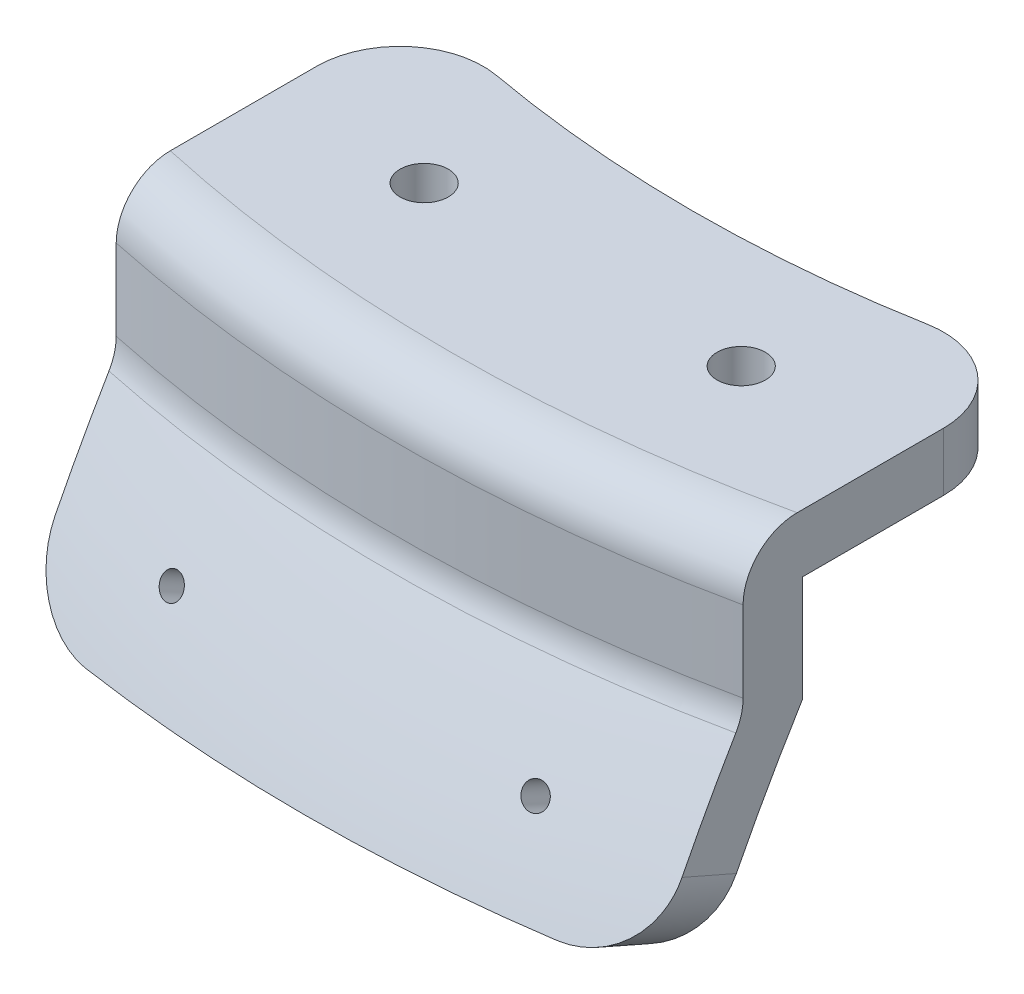
SolidWorks part; units mm, degrees
material "Polyether Polyol"
ref_plane "Front Plane" through (0, 0, 0) normal (0, 0, 1) x (1, 0, 0)
ref_plane "Top Plane" through (0, 0, 0) normal (0, 1, 0) x (1, 0, 0)
ref_plane "Right Plane" through (0, 0, 0) normal (1, 0, 0) x (0, 0, -1)
sketch "Sketch2" plane through (0, 0, 0) normal (1, 0, 0) x (0, 0, -1)
  line L0 (-174.1012, 207.3685) -> (-174.1012, 194.6685) construction
  line L1 (-192.235, 174.9156) -> (-185.8333, 172.084) construction
  line L2 (-181.1012, 214.3685) -> (-181.1012, 196.5948) construction
  line L3 (-181.1012, 214.3685) -> (-145.5262, 214.3685) construction
  line L4 (-145.5262, 214.3685) -> (-145.5262, 207.3685) construction
  line L5 (-145.5262, 207.3685) -> (-174.1012, 207.3685) construction
  line L12 (0, 89.8878) -> (0, 207.3685) construction
  line L13 (-174.1012, 207.3685) -> (-174.1012, 194.6685)
  line L14 (-192.235, 174.9156) -> (-185.8333, 172.084)
  line L15 (-181.1012, 214.3685) -> (-181.1012, 196.5948)
  line L16 (-181.1012, 214.3685) -> (-145.5262, 214.3685)
  line L17 (-145.5262, 214.3685) -> (-145.5262, 207.3685)
  line L18 (-145.5262, 207.3685) -> (-174.1012, 207.3685)
  arc A0 (-174.1012, 194.6685) -> (-185.8333, 172.084) centre (0, 89.8878) ccw construction
  arc A1 (-181.1012, 196.5948) -> (-192.235, 174.9156) centre (0, 89.8878) ccw construction
  arc A4 (-174.1012, 194.6685) -> (-185.8333, 172.084) centre (0, 89.8878) ccw
  arc A5 (-181.1012, 196.5948) -> (-192.235, 174.9156) centre (0, 89.8878) ccw
revolve "Revolve1" add sketch "Sketch2" angle 30 mid plane about L12 other way angle 30
fillet "Fillet1" radius 6.35 2 edges at (0, 196.5948, 181.1012) (0, 214.3685, 181.1012)
sketch "Sketch3" plane through (0, 214.3685, 0) normal (0, -1, 0) x (1, 0, 0)
  circle A2 centre (-19.05, 158.75) radius 3.5719 construction
  circle A3 centre (19.05, 158.75) radius 3.5719 construction
  circle A4 centre (19.05, 158.75) radius 2.9
  circle A5 centre (-19.05, 158.75) radius 2.9
  dimension "D1" = 5.8
extrude "Cut-Extrude1" cut sketch "Sketch3" along normal through all contours A4 | A5 region at (19.05, 214.3685, 158.75) region at (-19.05, 214.3685, 158.75)
sketch "Sketch4" plane through (0, 214.3685, 0) normal (0, 1, 0) x (1, 0, 0)
  line L0 (37.665, -140.5675) -> (45.2289, -168.7967) construction
  line L1 (37.665, -140.5675) -> (-37.665, -140.5675)
  line L2 (37.665, -140.5675) -> (37.665, -192.235)
  line L3 (37.665, -192.235) -> (-37.665, -192.235)
  line L4 (-37.665, -140.5675) -> (-37.665, -192.235)
  line L5 (-37.665, -140.5675) -> (-45.2289, -168.7967) construction
  arc A0 (-37.665, -140.5675) -> (37.665, -140.5675) centre (0, 0) ccw construction
  arc A1 (-49.7541, -185.6848) -> (49.7541, -185.6848) centre (0, 0) ccw construction
  point P5 (37.665, -140.5675)
  point P12 (37.665, -201.1133)
  point P16 (-37.665, -140.5675)
extrude "Cut-Extrude2" cut sketch "Sketch4" against normal through all flip side to cut
fillet "Fillet2" radius 10 4 edges at (-37.665, 210.8685, 140.5675) (37.665, 210.8685, 140.5675)
sketch "Sketch5" plane through (0, 0, 0) normal (-1, 0, 0) x (0, 0, 1)
  line L0 (0, 89.8878) -> (181.0525, 182.1386) construction
  line L2 (0, -200000) -> (0, 218797.9879) construction
  arc A0 (185.8333, 172.084) -> (174.1012, 194.6685) centre (0, 89.8878) ccw construction
  point P3 (169.9388, 179.5463)
  point P4 (0, 89.8878)
  point P5 (179.5114, 185.1028)
  dimension "D1" = 63
ref_plane "Plane1" through (0, 71.3612, -36.3604) normal (0, 0.891, -0.454) x (0, 0.454, 0.891)
sketch "Sketch6" plane through (0, 71.3612, -36.3604) normal (0, 0.891, -0.454) x (0, 0.454, 0.891)
  line L0 (216.935, 18.9794) -> (275.7942, 24.1289) construction
  line L2 (216.935, 18.9794) -> (275.7942, 24.1289)
  line L3 (216.935, 18.9794) -> (216.8043, 20.4736)
  line L4 (275.7942, 24.1289) -> (275.6635, 25.6232)
  line L5 (216.8043, 20.4736) -> (275.6635, 25.6232)
  line L6 (40.8082, 0) -> (244.0082, 0) construction
  ellipse E0 centre (88.3777, 0) end of major axis (88.3777, 145.5262) minor radius 129.6648 construction
  point P5 (260.6405, 66.5442)
  point P6 (263.1848, 88.2284)
  point P7 (214.7945, 21.0289)
  point P10 (218.7784, 80.0906)
  point P11 (265.6813, 84.2561)
  point P12 (217.1018, 80.0906)
  point P13 (218.0425, 0)
  point P20 (261.8476, 16.122)
  point P21 (217.2119, 2.7785)
  point P23 (275.7942, 27.0178)
  dimension "D1" = 5
  dimension "D2" = 1.5
revolve "Cut-Revolve1" cut sketch "Sketch6" angle 360 about L0
mirror "Mirror1" about plane through (0, 0, 0) normal (1, 0, 0) of "Cut-Revolve1"
